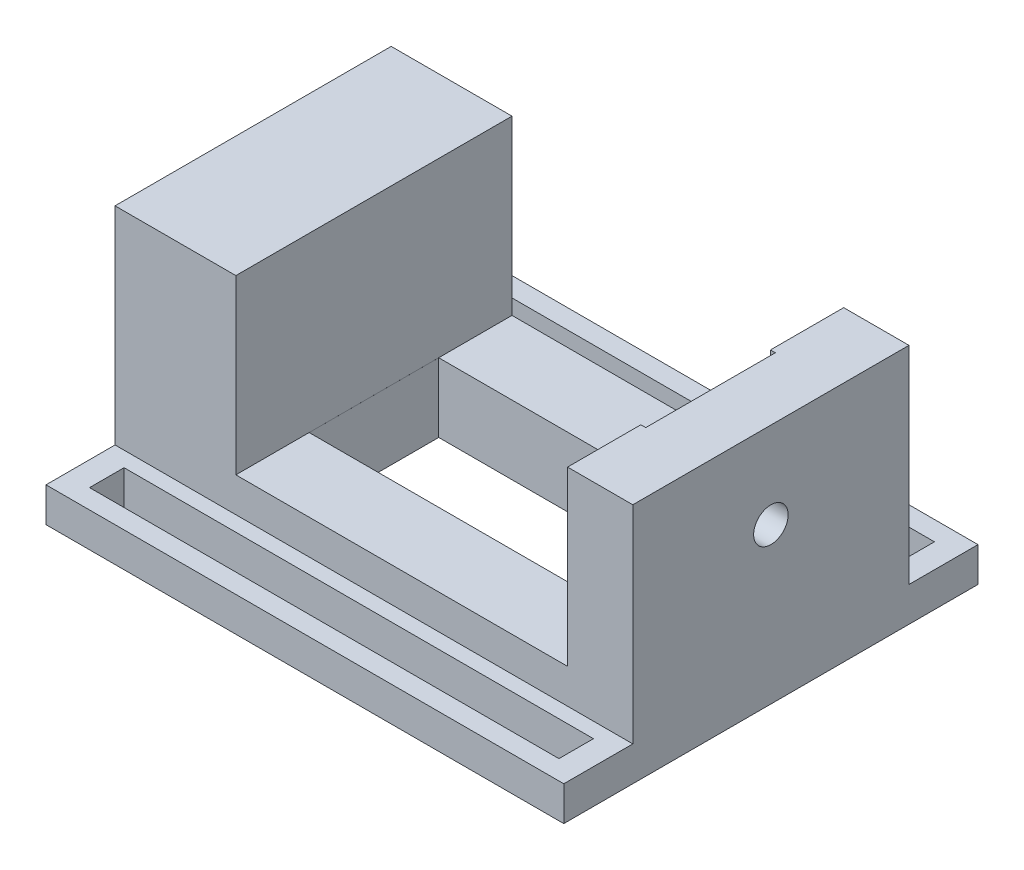
SolidWorks part; units mm, degrees
ref_plane "Спереди" through (0, 0, 0) normal (0, 0, 1) x (1, 0, 0)
ref_plane "Сверху" through (0, 0, 0) normal (0, 1, 0) x (1, 0, 0)
ref_plane "Справа" through (0, 0, 0) normal (1, 0, 0) x (0, 0, -1)
sketch "Эскиз1" plane through (0, 0, 0) normal (0, 1, 0) x (1, 0, 0)
  line L1 (-75, 40) -> (75, 40)
  line L2 (-75, 40) -> (-75, -40)
  line L3 (-75, -40) -> (75, -40)
  line L4 (75, 40) -> (75, -40)
  line L5 (-75, 40) -> (75, -40) construction
  line L6 (-75, -40) -> (75, 40) construction
  point P0 (0, 0)
extrude "Бобышка-Вытянуть1" add sketch "Эскиз1" along normal blind 60
sketch "Эскиз2" plane through (0, 0, 0) normal (0, -1, 0) x (1, 0, 0)
  line L0 (-75, 0) -> (75, 0) construction
  line L1 (75, -60) -> (-75, -60)
  line L2 (75, -60) -> (75, 60)
  line L3 (75, 60) -> (-75, 60)
  line L4 (-75, -60) -> (-75, 60)
  line L5 (75, -60) -> (-75, 60) construction
  line L6 (75, 60) -> (-75, -60) construction
  line L7 (-67.9915, 44.3932) -> (67.9915, 44.3932)
  line L8 (-67.9915, 44.3932) -> (-67.9915, 54.3932)
  line L9 (-67.9915, 54.3932) -> (67.9915, 54.3932)
  line L10 (67.9915, 44.3932) -> (67.9915, 54.3932)
  line L11 (67.9915, -44.3932) -> (67.9915, -54.3932)
  line L12 (-67.9915, -54.3932) -> (67.9915, -54.3932)
  line L13 (-67.9915, -44.3932) -> (-67.9915, -54.3932)
  line L14 (-67.9915, -44.3932) -> (67.9915, -44.3932)
  point P0 (0, 0)
extrude "Бобышка-Вытянуть2" add sketch "Эскиз2" along normal blind 10
sketch "Эскиз3" plane through (0, 0, 40) normal (0, 0, 1) x (1, 0, 0)
  line L0 (-75, 60) -> (75, 60) construction
  line L1 (-40, 60) -> (56.093, 60)
  line L2 (-40, 60) -> (-40, 10)
  line L3 (-40, 10) -> (56.093, 10)
  line L4 (56.093, 60) -> (56.093, 10)
  point P6 (0, 0)
extrude "Вырез-Вытянуть1" cut sketch "Эскиз3" against normal through all
sketch "Эскиз5" plane through (0, -10, 0) normal (0, -1, 0) x (1, 0, 0)
  line L0 (-75, 0) -> (75, 0) construction
  line L2 (-39.995, 18.7674) -> (-39.995, -18.7674)
  line L3 (-39.995, -18.7674) -> (57.5152, -18.7674)
  line L4 (57.5152, 18.7674) -> (57.5152, -18.7674)
  line L5 (-75, 60) -> (-75, -60) construction
  line L6 (75, -60) -> (75, 60) construction
  line L7 (-39.995, 18.7674) -> (57.5152, 18.7674)
  point P0 (0, 0)
  point P2 (62.6657, 17.2317)
  point P6 (37.5953, 0)
  point P7 (-39.995, 0)
  point P15 (57.5152, 0)
  point P16 (-39.995, 0)
  point P17 (58.5587, 16.1827)
  point P18 (57.5152, 18.7674)
extrude "Вырез-Вытянуть2" cut sketch "Эскиз5" against normal through all
sketch "Эскиз6" plane through (75, 0, 0) normal (1, 0, 0) x (0, 0, -1)
  line L0 (0, 60) -> (0, -10) construction
  line L1 (-40, 60) -> (40, 60) construction
  line L2 (60, -10) -> (-60, -10) construction
  circle A0 centre (0, 35) radius 5
extrude "Вырез-Вытянуть3" cut sketch "Эскиз6" against normal blind 30
